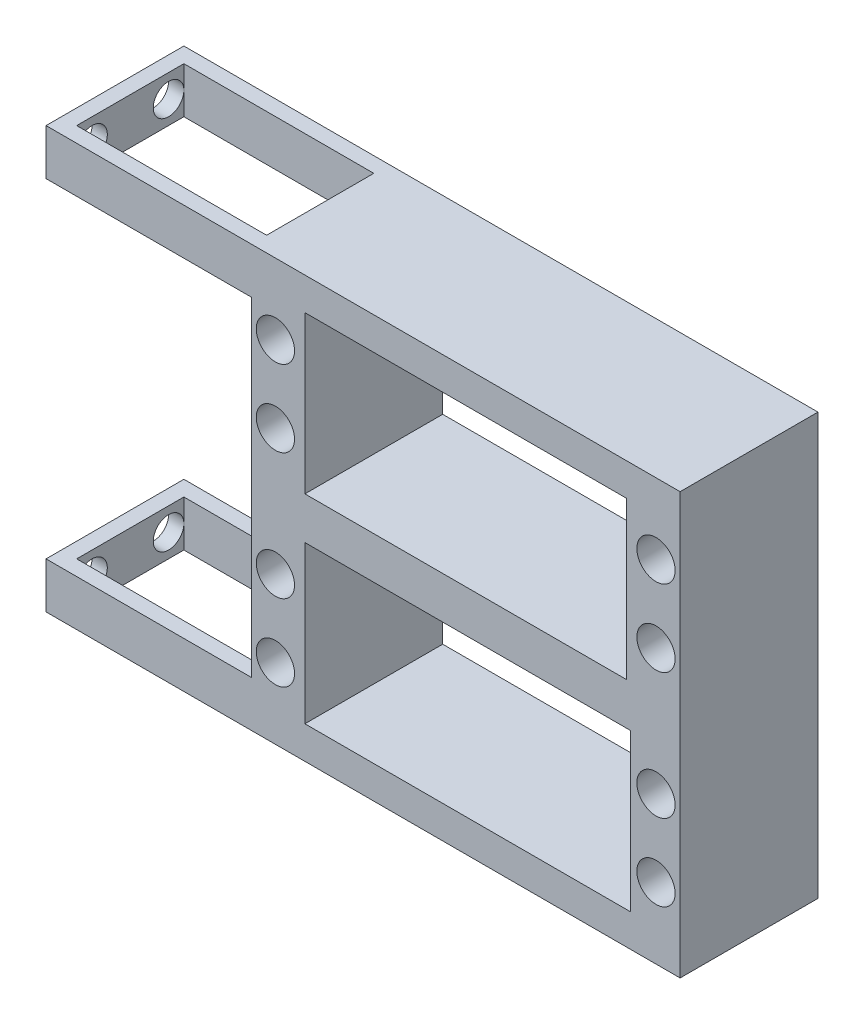
SolidWorks part; units mm, degrees
ref_plane "Front Plane" through (0, 0, 0) normal (0, 0, 1) x (1, 0, 0)
ref_plane "Top Plane" through (0, 0, 0) normal (0, 1, 0) x (1, 0, 0)
ref_plane "Right Plane" through (0, 0, 0) normal (1, 0, 0) x (0, 0, -1)
sketch "Sketch2" plane through (0, 0, 0) normal (0, 0, 1) x (1, 0, 0)
  line L0 (0, -30.25) -> (0, 30.25) construction
  line L1 (0, 55) -> (56, 55)
  line L2 (0, 55) -> (0, 0)
  line L3 (0, 0) -> (56, 0)
  line L4 (56, 55) -> (56, 0)
  line L5 (33, 0) -> (-33, 0) construction
  line L7 (7, 50.75) -> (49, 50.75)
  line L8 (7, 50.75) -> (7, 30.25)
  line L9 (7, 30.25) -> (49, 30.25)
  line L10 (49, 50.75) -> (49, 30.25)
  line L11 (7, 24.75) -> (49.5, 24.75)
  line L12 (7, 24.75) -> (7, 4.25)
  line L13 (7, 4.25) -> (49.5, 4.25)
  line L14 (49.5, 24.75) -> (49.5, 4.25)
  dimension "D1" = 55
  dimension "D2" = 56
  dimension "D3" = 42
  dimension "D4" = 20.5
  dimension "D5" = 5.5
  dimension "D6" = 42.5
  dimension "D7" = 20.5
  dimension "D8" = 7
  dimension "D9" = 4.25
  dimension "D10" = 7
extrude "Boss-Extrude1" add sketch "Sketch2" along normal blind 18
sketch "Sketch3" plane through (0, 0, 18) normal (0, 0, 1) x (1, 0, 0)
  line L0 (49, 50.75) -> (7, 50.75) construction
  line L1 (7, 50.75) -> (7, 30.25) construction
  line L4 (28, 55) -> (28, 0) construction
  line L5 (56, 55) -> (0, 55) construction
  line L6 (55, 0) -> (-55, 0) construction
  line L8 (28, 27.5) -> (0, 27.5) construction
  line L9 (0, -55) -> (0, 55) construction
  circle A0 centre (3.15, 45.75) radius 2.5
  circle A1 centre (3.15, 35.75) radius 2.5
  circle A6 centre (52.85, 35.75) radius 2.5
  circle A7 centre (52.85, 45.75) radius 2.5
  circle A8 centre (3.15, 19.25) radius 2.5
  circle A9 centre (3.15, 9.25) radius 2.5
  circle A10 centre (52.85, 9.25) radius 2.5
  circle A11 centre (52.85, 19.25) radius 2.5
  dimension "D1" = 10
  dimension "D2" = 5
  dimension "D3" = 5
  dimension "D4" = 5
  dimension "D5" = 3.85
  dimension "D6" = 3.85
extrude "Cut-Extrude1" cut sketch "Sketch3" against normal blind 10
sketch "Sketch5" plane through (0, 0, 0) normal (-1, 0, 0) x (0, 0, 1)
  line L0 (0, -30.25) -> (0, 30.25) construction
  line L1 (0, 55) -> (2, 55)
  line L2 (0, 55) -> (0, 49)
  line L3 (0, 49) -> (2, 49)
  line L4 (2, 55) -> (2, 49)
  line L5 (18, 55) -> (0, 55) construction
  line L6 (9.9, 0) -> (-9.9, 0) construction
  line L7 (18, 55) -> (16, 55)
  line L8 (18, 55) -> (18, 49)
  line L9 (18, 49) -> (16, 49)
  line L10 (16, 55) -> (16, 49)
  line L11 (0, 0) -> (2, 0)
  line L12 (0, 0) -> (0, 6)
  line L13 (0, 6) -> (2, 6)
  line L14 (2, 0) -> (2, 6)
  line L15 (18, 0) -> (16, 0)
  line L16 (18, 0) -> (18, 6)
  line L17 (18, 6) -> (16, 6)
  line L18 (16, 0) -> (16, 6)
  line L19 (18, 55) -> (18, 0) construction
  dimension "D1" = 2
  dimension "D2" = 2
  dimension "D3" = 6
  dimension "D4" = 6
  dimension "D5" = 2
  dimension "D6" = 2
  dimension "D7" = 6
  dimension "D8" = 6
extrude "Boss-Extrude2" add sketch "Sketch5" along normal blind 26.8
sketch "Sketch6" plane through (0, 0, 2) normal (0, 0, 1) x (1, 0, 0)
  line L0 (-26.8, 49) -> (0, 49) construction
  line L1 (-24.8, 49) -> (-26.8, 49)
  line L2 (-24.8, 49) -> (-24.8, 55)
  line L3 (-24.8, 55) -> (-26.8, 55)
  line L4 (-26.8, 49) -> (-26.8, 55)
  line L5 (56, 55) -> (-26.8, 55) construction
  line L6 (-26.8, 55) -> (-26.8, 49) construction
  line L7 (9.9, 0) -> (-9.9, 0) construction
  line L8 (-26.8, 6) -> (-24.8, 6)
  line L9 (-26.8, 6) -> (-26.8, 0)
  line L10 (-26.8, 0) -> (-24.8, 0)
  line L11 (-24.8, 6) -> (-24.8, 0)
  dimension "D1" = 2
  dimension "D2" = 2
extrude "Boss-Extrude3" add sketch "Sketch6" along normal up to next
sketch "Sketch7" plane through (-26.8, 0, 0) normal (-1, 0, 0) x (0, 0, 1)
  line L0 (0, -30.25) -> (0, 30.25) construction
  line L1 (18, 55) -> (0, 55) construction
  line L2 (18, 49) -> (18, 55) construction
  line L3 (18, 0) -> (18, 6) construction
  line L4 (18, 6) -> (0, 6) construction
  circle A0 centre (4, 52) radius 2
  circle A1 centre (14, 52) radius 2
  circle A2 centre (4, 3) radius 2
  circle A3 centre (14, 3) radius 2
  dimension "D1" = 4
  dimension "D2" = 4
  dimension "D3" = 4
  dimension "D4" = 3
  dimension "D5" = 4
  dimension "D6" = 3
  dimension "D7" = 4
  dimension "D8" = 4
  dimension "D9" = 4
  dimension "D10" = 4
  dimension "D11" = 3
  dimension "D12" = 3
extrude "Cut-Extrude2" cut sketch "Sketch7" against normal blind 10
